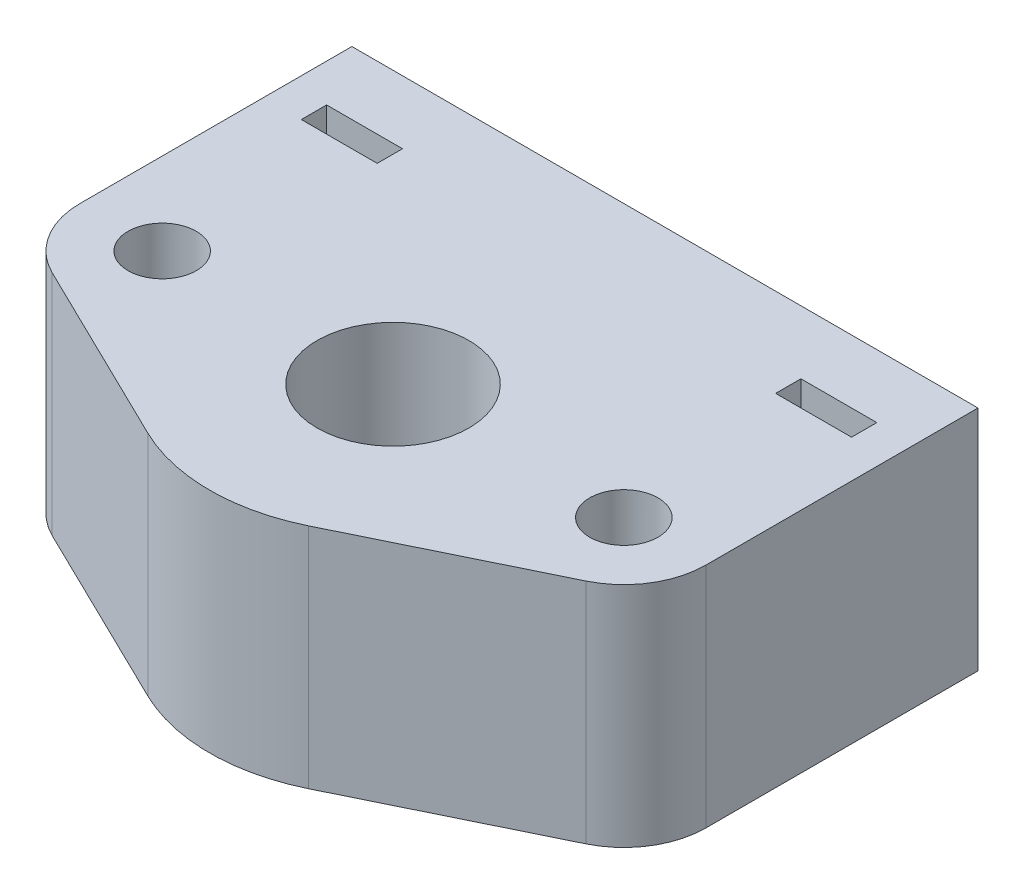
SolidWorks part; units mm, degrees
ref_plane "Front Plane" through (0, 0, 0) normal (0, 0, 1) x (1, 0, 0)
ref_plane "Top Plane" through (0, 0, 0) normal (0, 1, 0) x (1, 0, 0)
ref_plane "Right Plane" through (0, 0, 0) normal (1, 0, 0) x (0, 0, -1)
sketch "Sketch1" plane through (0, 0, 0) normal (0, 1, 0) x (1, 0, 0)
  line L0 (-24.75, 0) -> (-24.75, -21.5)
  line L2 (-24.75, 0) -> (0, 0)
  line L3 (0, 0) -> (0, -15.5)
  line L4 (0, -27.5) -> (0, -36)
  line L7 (-21.0993, -27.3422) -> (-6.3562, -34.5326)
  line L9 (-18.25, -21.5) -> (0, -21.5) construction
  circle A0 centre (-18.25, -21.5) radius 2.7
  arc A1 (0, -15.5) -> (0, -27.5) centre (0, -21.5) ccw
  arc A2 (-6.3562, -34.5326) -> (0, -36) centre (0, -21.5) ccw
  arc A3 (-24.75, -21.5) -> (-21.0993, -27.3422) centre (-18.25, -21.5) ccw
  dimension "D3" = 6
  dimension "D6" = 14.5
  dimension "D7" = 6.5
  dimension "D2" = 5.4
  dimension "D1" = 21.5
  dimension "D8" = 18.25
extrude "Boss-Extrude1" add sketch "Sketch1" along normal blind 12 and the other way blind 6
sketch "Sketch3" plane through (0, 0, 0) normal (0, 0, -1) x (-1, 0, 0)
  line L0 (0, -6) -> (0, 12) construction
  line L2 (18.75, 12) -> (18.75, 6) construction
  line L3 (0, 12) -> (24.75, 12) construction
  line L4 (18.75, 6) -> (24.75, 6) construction
  line L5 (24.75, 12) -> (24.75, -6) construction
  line L6 (0, 1.7) -> (0, -1.7)
  circle A0 centre (18.75, 6) radius 1.7
  arc A1 (0, 1.7) -> (0, -1.7) centre (0, 0) cw
  dimension "D1" = 3.4
  dimension "D2" = 6
extrude "Cut-Extrude1" cut sketch "Sketch3" against normal blind 10
sketch "Sketch4" plane through (0, 0, 0) normal (0, 0, -1) x (-1, 0, 0)
  line L0 (15.75, 9) -> (15.75, 12)
  line L1 (15.75, 3) -> (21.75, 3)
  line L2 (15.75, 3) -> (15.75, 9)
  line L3 (15.75, 9) -> (21.75, 9) construction
  line L4 (21.75, 3) -> (21.75, 9)
  line L5 (15.75, 3) -> (21.75, 9) construction
  line L6 (15.75, 9) -> (21.75, 3) construction
  line L7 (0, 12) -> (24.75, 12) construction
  line L8 (21.75, 9) -> (21.75, 12)
  line L9 (21.75, 12) -> (15.75, 12)
  line L10 (0, 3) -> (3, 3)
  line L11 (0, 1.7) -> (0, 12) construction
  line L12 (3, 3) -> (3, 0)
  line L13 (0, -6) -> (24.75, -6) construction
  line L14 (3, -6) -> (0, -6)
  line L15 (0, -6) -> (0, 3)
  line L16 (3, 0) -> (3, -6)
  line L17 (0, 0) -> (3, 0) construction
  point P0 (18.75, 6)
  dimension "D1" = 6
  dimension "D2" = 3
extrude "Cut-Extrude2" cut sketch "Sketch4" against normal blind 2 from offset 5 offset against normal yes
sketch "Sketch6" plane through (0, -6, 0) normal (0, -1, 0) x (1, 0, 0)
  line L1 (-14, 23.9537) -> (-18.25, 26.4075)
  line L2 (-18.25, 26.4075) -> (-22.5, 23.9537)
  line L3 (-22.5, 23.9537) -> (-22.5, 19.0463)
  line L4 (-22.5, 19.0463) -> (-18.25, 16.5925)
  line L5 (-18.25, 16.5925) -> (-14, 19.0463)
  line L6 (-14, 19.0463) -> (-14, 23.9537)
  circle A0 centre (-18.25, 21.5) radius 4.25 construction
  dimension "D1" = 8.5
extrude "Cut-Extrude3" cut sketch "Sketch6" against normal blind 10
mirror "Mirror1" about plane through (0, -6, 0) normal (1, 0, 0) of bodies 108 103
equation "\"M3_d\"= 3.4"
equation "\"M3_nut_m\"= 2"
equation "\"M3_nut_s\" = 6"
equation "\"t\"= 3"
equation "\"D1@Boss-Extrude1\"=\"M3_nut_s\" + 2 * \"t\""
equation "\"D1@Sketch3\"=\"M3_d\""
equation "\"D1@Sketch4\"=\"M3_nut_s\""
equation "\"D1@Cut-Extrude2\"=\"M3_nut_m\""
equation "\"D2@Sketch3\"=\"M3_nut_s\" / 2 + \"t\""
equation "\"D19@Cut-Extrude5\"=(10 - \"M3_nut_m\") / 2"
equation "\"D2@Boss-Extrude1\"=0.5 * \"M3_nut_s\" + \"t\""
equation "\"D2@Sketch4\"=\"M3_nut_s\" / 2"
equation "\"M5_d\"= 5.4"
equation "\"D2@Sketch1\"=\"M5_d\""
equation "\"M5_nut_s\"= 8.5"
equation "\"D1@Sketch6\"=\"M5_nut_s\""
